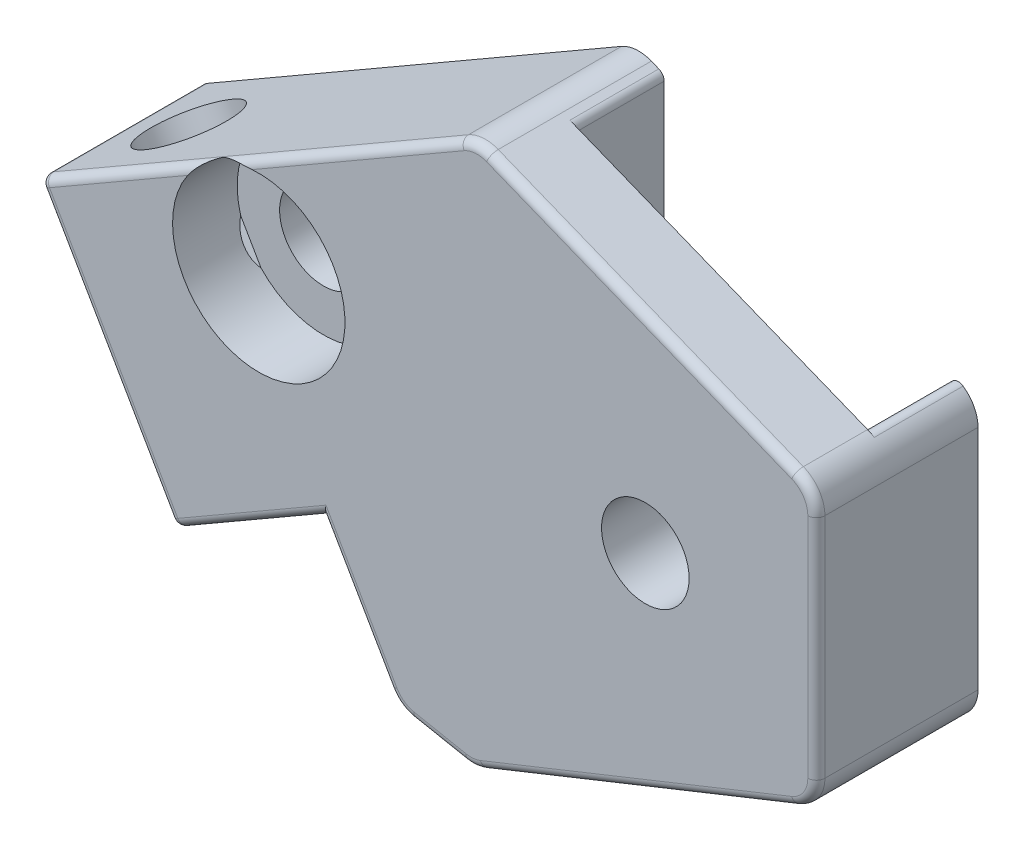
SolidWorks part; units mm, degrees
ref_plane "Front Plane" through (0, 0, 0) normal (0, 0, 1) x (1, 0, 0)
ref_plane "Top Plane" through (0, 0, 0) normal (0, 1, 0) x (1, 0, 0)
ref_plane "Right Plane" through (0, 0, 0) normal (1, 0, 0) x (0, 0, -1)
sketch "Sketch1" plane through (0, 0, 0) normal (0, 0, 1) x (1, 0, 0)
  line L0 (-10.5833, 0) -> (-2.6458, 0) construction
  line L1 (5.2917, -6.35) -> (-10.5833, -12.7)
  line L2 (5.2917, -6.35) -> (5.2917, 6.35)
  line L3 (5.2917, 6.35) -> (-10.5833, 12.7)
  line L4 (-10.5833, -12.7) -> (-10.5833, 12.7)
  line L5 (5.2917, -6.35) -> (-10.5833, 12.7) construction
  line L6 (5.2917, 6.35) -> (-10.5833, -12.7) construction
  line L7 (-2.6458, 0) -> (5.2917, 0) construction
  circle A0 centre (-2.6458, 0) radius 2.032
  point P0 (0, 0)
  dimension "D2" = 4.064
  dimension "D1" = 15.875
  dimension "D3" = 12.7
  dimension "D4" = 25.4
extrude "Boss-Extrude1" add sketch "Sketch1" along normal blind 3.375
sketch "Sketch2" plane through (0, 0, 3.375) normal (0, 0, 1) x (1, 0, 0)
  line L0 (-10.5833, -12.7) -> (5.2917, -6.35) construction
  line L2 (-10.5833, 12.7) -> (-10.5833, -12.7)
  line L4 (-9.2708, 12.175) -> (-9.2708, -12.175)
  line L5 (5.2917, 6.35) -> (-10.5833, 12.7) construction
  line L7 (5.2917, 6.35) -> (5.2917, -6.35)
  line L9 (3.9792, 6.875) -> (3.9792, -6.875)
  line L10 (-10.5833, -12.7) -> (-9.2708, -12.175)
  line L11 (5.2917, 6.35) -> (3.9792, 6.875)
  line L12 (3.9792, -6.875) -> (5.2917, -6.35)
  line L13 (-9.2708, 12.175) -> (-10.5833, 12.7)
  circle A0 centre (-2.6458, 0) radius 6.625 construction
  dimension "D2" = 13.25
extrude "Boss-Extrude2" add sketch "Sketch2" along normal blind 4.125
sketch "Sketch4" plane through (0, 0, 0) normal (0, 0, -1) x (-1, 0, 0)
  line L0 (10.5833, 12.7) -> (30.836, 1.0071)
  line L2 (24.486, -9.9914) -> (10.5833, -12.7)
  line L3 (10.5833, -12.7) -> (10.5833, 12.7)
  line L4 (30.836, 1.0071) -> (24.486, -9.9914)
  circle A0 centre (20.5846, 2.3012) radius 2.032
  circle A1 centre (2.6458, 0) radius 2.032 construction
  dimension "D1" = 17.9387
  dimension "D2" = 2.3012
  dimension "D3" = 30
  dimension "D4" = 9.525
  dimension "D5" = 12.7
extrude "Boss-Extrude3" add sketch "Sketch4" against normal up to surface (7.5 mm away) up to face at (-9.9271, 0, 7.5)
sketch "Sketch5" plane through (-8.1451, 14.1077, 0) normal (-0.5, 0.866, 0) x (0.866, 0.5, 0)
  line L0 (-26.2012, -3.75) -> (-22.4512, -3.75) construction
  line L1 (-26.2012, -7.5) -> (-26.2012, 0) construction
  line L2 (-22.4512, -3.75) -> (-22.4512, 0) construction
  line L3 (-26.2012, 0) -> (-2.8154, 0) construction
  circle A0 centre (-22.4512, -3.75) radius 2.032
  dimension "D1" = 4.064
extrude "Cut-Extrude1" cut sketch "Sketch5" against normal through all
ref_plane "Plane1" through (-1.7951, 3.1092, 0) normal (-0.5, 0.866, 0) x (0.866, 0.5, 0)
sketch "Sketch6" plane through (-1.7951, 3.1092, 0) normal (-0.5, 0.866, 0) x (0.866, 0.5, 0)
  line L0 (-18.2637, -7.5) -> (-18.2637, 0)
  line L1 (-26.2012, -7.5) -> (-2.8154, -7.5) construction
  line L2 (-26.2012, 0) -> (-2.8154, 0) construction
  line L3 (-18.2637, 0) -> (-26.2012, 0)
  line L4 (-26.2012, 0) -> (-26.2012, -7.5)
  line L5 (-26.2012, -7.5) -> (-18.2637, -7.5)
  dimension "D1" = 7.9375
extrude "Cut-Extrude2" cut sketch "Sketch6" against normal through all
fillet "Fillet1" radius 1.5875 5 edges at (5.2917, -6.35, 3.75) (5.2917, 6.35, 3.75) (-10.5833, 12.7, 3.75) (-14.1589, -12.0034, 3.75) (-10.5833, -12.7, 3.75)
fillet "Fillet2" radius 0.3969 19 edges at (3.9792, -6.875, 5.4375) (3.9792, 6.875, 5.4375) (5.0187, 6.1652, 0) (5.2917, 0, 0) (5.0187, -6.1652, 0) (-2.9277, -9.6377, 0) (-2.7869, 9.5814, 0) (-16.0662, -8.6999, 0) (-14.0677, -11.8757, 0) (-12.2458, -12.3761, 0) (-10.5897, -12.6329, 0) (-21.0434, 6.6609, 0) (-10.5707, 12.5232, 0) (-21.0489, -8.007, 0) (-27.661, -4.4921, 0) (-30.836, 1.0071, 3.75) (-24.486, -9.9914, 3.75) (-9.2708, -12.175, 5.4375) (-9.2708, 12.175, 5.4375)
mirror "Mirror1" about plane through (0, 0, 7.5) normal (0, 0, 1) of bodies 106
delete or keep bodies "Body-Delete/Keep 1" type delete bodies bodies 106
sketch "Sketch7" plane through (0, 0, 15) normal (0, 0, 1) x (1, 0, 0)
  circle A0 centre (-20.5846, 2.3012) radius 4
  dimension "D1" = 8
extrude "Cut-Extrude3" cut sketch "Sketch7" against normal blind 3
